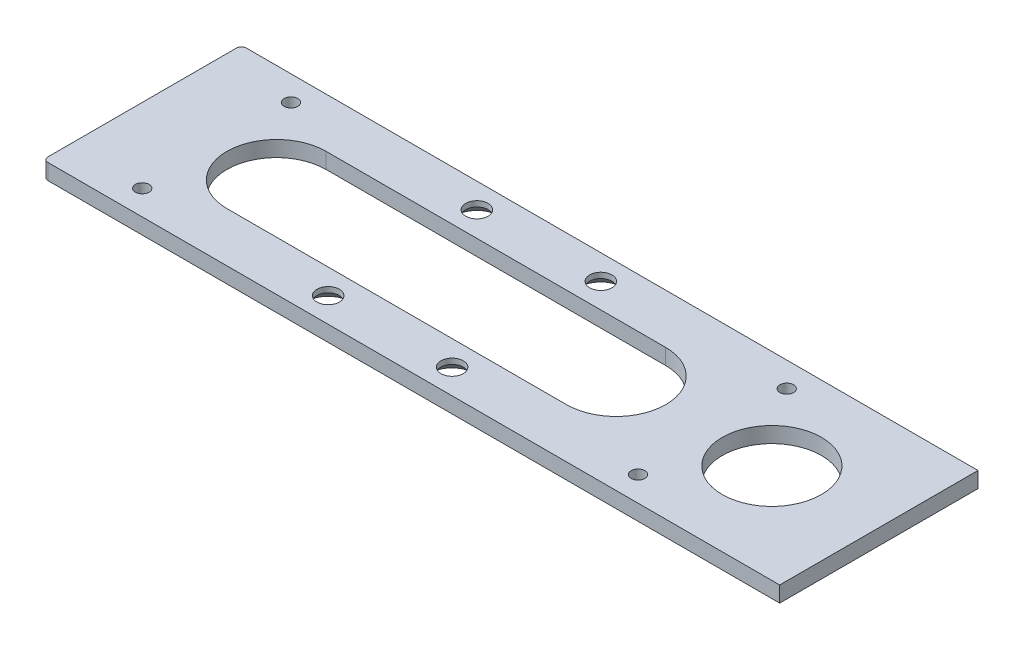
SolidWorks part; units mm, degrees
note: The reader was unsure of these and kept them because the rebuilt part matched: thickness of "Brida base1", "Chapa metálica1", "Chapa metálica2", "Chapa metálica5", "Sheet-Metal6".
ref_plane "Alzado" through (0, 0, 0) normal (0, 0, 1) x (1, 0, 0)
ref_plane "Planta" through (0, 0, 0) normal (0, 1, 0) x (1, 0, 0)
ref_plane "Vista lateral" through (0, 0, 0) normal (1, 0, 0) x (0, 0, -1)
sketch "Croquis1" plane through (0, 0, 0) normal (0, 1, 0) x (1, 0, 0)
  line L1 (-149.7778, 34.4444) -> (147.3722, 34.4444)
  line L2 (-149.7778, 34.4444) -> (-149.7778, -45.5556)
  line L3 (-149.7778, -45.5556) -> (147.3722, -45.5556)
  line L4 (147.3722, 34.4444) -> (147.3722, -45.5556)
  dimension "k" = 297.15
  dimension "D2" = 80
base flange "Brida base1" sketch "Croquis1" thickness 6.35 reverse thickness direction no parameters "D1"=10
fillet "Redondeo1" radius 2 2 edges at (-149.7778, -3.175, -34.4444) (-149.7778, -3.175, 45.5556)
hole_wizard "Taladro de margen para M51" positions "Croquis7" profile "Croquis6" hole size "M5" standard "Ansi Metric" end condition through all
sketch "Croquis7" plane through (0, 0, 0) normal (0, 1, 0) x (1, 0, 0)
  line L0 (-149.7778, 32.4444) -> (-149.7778, -43.5556) construction
  line L11 (-149.7778, -5.5556) -> (147.3722, -5.5556) construction
  line L12 (147.3722, -45.5556) -> (147.3722, 34.4444) construction
  point P0 (-119.7778, 24.4444)
  point P2 (-119.7778, -35.5556)
  point P4 (80.2222, -35.5556)
  point P45 (80.2222, 24.4444)
  dimension "D1" = 30
  dimension "D2" = 30
  dimension "D3" = 60
sketch "Croquis6" plane through (-119.7778, 0, -24.4444) normal (1, 0, 0) x (0, 0, 1)
  line L0 (0, 0) -> (0, 6.35)
  line L1 (0, 6.35) -> (2.75, 6.35)
  line L2 (2.75, 6.35) -> (2.75, 0)
  line L5 (2.75, 0) -> (0, 0)
  line L11 (0, -6.35) -> (0, 107.95) construction
  dimension "Diámetro de taladro hasta el siguiente" = 5.5
  dimension "Profundidad de taladro hasta el siguiente" = 6.35
sketch "Croquis8" plane through (0, 0, 0) normal (0, 1, 0) x (1, 0, 0)
  line L0 (-149.7778, -5.5556) -> (147.3722, -5.5556) construction
  line L1 (-149.7778, 32.4444) -> (-149.7778, -43.5556) construction
  line L2 (147.3722, -45.5556) -> (147.3722, 34.4444) construction
  line L3 (-0.2028, 34.4444) -> (-0.2028, -45.5556) construction
  line L5 (-147.7778, -45.5556) -> (147.3722, -45.5556) construction
  line L6 (147.3722, 34.4444) -> (-147.7778, 34.4444) construction
sketch "Croquis9" plane through (0, -6.35, 0) normal (0, -1, 0) x (-1, 0, 0)
  line L0 (-41.3891, -5.5556) -> (95.6281, -5.5556) construction
  line L1 (-41.3891, 14.4444) -> (95.6281, 14.4444)
  line L2 (-41.3891, -25.5556) -> (95.6281, -25.5556)
  line L3 (149.7778, -5.5556) -> (-147.3722, -5.5556) construction
  line L4 (149.7778, 32.4444) -> (149.7778, -43.5556) construction
  line L5 (-147.3722, -45.5556) -> (-147.3722, 34.4444) construction
  line L6 (-147.3722, 34.4444) -> (147.7778, 34.4444) construction
  arc A0 (-41.3891, 14.4444) -> (-41.3891, -25.5556) centre (-41.3891, -5.5556) ccw
  arc A1 (95.6281, -25.5556) -> (95.6281, 14.4444) centre (95.6281, -5.5556) ccw
  circle A2 centre (-104.2099, -5.5556) radius 20
  point P2 (27.1195, -5.5556)
  dimension "D2" = 40
  dimension "D1" = 20
extrude "Cortar-Extruir1" cut sketch "Croquis9" against normal blind 10 contours A2 | L1 A1 L2 A0 normal cut yes
sketch "Sketch1" plane through (0, -6.35, 0) normal (0, -1, 0) x (1, 0, 0)
  line L0 (-149.7778, 5.5556) -> (-64.7778, 5.5556) construction
  line L1 (-64.7778, 5.5556) -> (-64.7778, 45.5556) construction
  line L2 (-64.7778, 5.5556) -> (-64.7778, -34.4444) construction
  line L3 (-64.7778, 5.5556) -> (25.2222, 5.5556) construction
  line L4 (-149.7778, 43.5556) -> (-149.7778, -32.4444)
  line L5 (-147.7778, -34.4444) -> (147.3722, -34.4444)
  line L6 (147.3722, -34.4444) -> (147.3722, 45.5556)
  line L7 (147.3722, 45.5556) -> (-147.7778, 45.5556)
  line L8 (-149.7778, 43.5556) -> (-149.7778, -32.4444) construction
  line L9 (-147.7778, -34.4444) -> (147.3722, -34.4444) construction
  line L10 (147.3722, -34.4444) -> (147.3722, 45.5556) construction
  line L11 (147.3722, 45.5556) -> (-147.7778, 45.5556) construction
  line L12 (25.2222, 5.5556) -> (25.2222, 45.5556) construction
  line L13 (25.2222, 5.5556) -> (25.2222, -34.4444) construction
  line L14 (41.3891, 25.5556) -> (-95.6281, 25.5556) construction
  line L15 (41.3891, -14.4444) -> (-95.6281, -14.4444) construction
  line L16 (41.3891, 25.5556) -> (-95.6281, 25.5556) construction
  line L17 (41.3891, -14.4444) -> (-95.6281, -14.4444) construction
  line L18 (-64.7778, -34.4444) -> (-64.7778, -24.4444) construction
  line L19 (-64.7778, -24.4444) -> (-44.7778, -24.4444) construction
  line L20 (25.2222, -34.4444) -> (25.2222, -24.4444)
  line L21 (25.2222, -24.4444) -> (5.2222, -24.4444)
  circle A0 centre (-44.7778, -24.4444) radius 4.5
  circle A1 centre (5.2222, -24.4444) radius 4.5
  arc A2 (-149.7778, -32.4444) -> (-147.7778, -34.4444) centre (-147.7778, -32.4444) ccw
  arc A3 (-147.7778, 45.5556) -> (-149.7778, 43.5556) centre (-147.7778, 43.5556) ccw
  arc A4 (-149.7778, -32.4444) -> (-147.7778, -34.4444) centre (-147.7778, -32.4444) ccw construction
  arc A5 (-147.7778, 45.5556) -> (-149.7778, 43.5556) centre (-147.7778, 43.5556) ccw construction
  circle A6 centre (5.2222, 35.5556) radius 4.5
  circle A7 centre (-44.7778, 35.5556) radius 4.5
  dimension "D7" = 9
  dimension "D8" = 9
  dimension "D2" = 85
  dimension "D3" = 90
  dimension "D4" = 10
  dimension "D5" = 20
  dimension "D6" = 20
  dimension "D1" = 0
hole_wizard "CSK for M8 Oval Head Machine Screw1" positions "3DSketch1" profile "Sketch2" countersink size "M8" standard "ANSI Metric"
sketch3d "3DSketch1"
  point P0 (-44.7778, -6.35, -24.4444)
  point P3 (5.2222, -6.35, -24.4444)
  point P6 (5.2222, -6.35, 35.5556)
  point P9 (-44.7778, -6.35, 35.5556)
sketch "Sketch2" plane through (-44.7778, -6.35, -24.4444) normal (1, 0, 0) x (0, 0, -1)
  line L0 (0, 0) -> (0, 9.0529)
  line L1 (0, 9.0529) -> (4.5, 6.349)
  line L2 (4.5, 6.349) -> (4.5, 4.15)
  line L3 (4.5, 4.15) -> (8.65, 0)
  line L5 (8.65, 0) -> (0, 0)
  line L6 (-4.5, 4.15) -> (-8.65, 0) construction
  line L10 (0, 9.0529) -> (-4.5, 6.349) construction
  line L11 (0, -6.35) -> (0, 107.95) construction
  dimension "Hole Dia." = 9
  dimension "Hole Depth" = 6.349
  dimension "Near C'Sink Dia." = 17.3
  dimension "Near C'Sink Angle" = 90
  dimension "Drill Angle" = 118
sketch "Líneas de pliegue1" [suppressed] plane through (0, 0, 0) normal (0, 1, 0) x (1, 0, 0)
sketch "Cuadro delimitador1" [suppressed] plane through (0, 0, 0) normal (0, 1, 0) x (1, 0, 0)
sheet metal parameters "Chapa metálica1" thickness 6.35 parameters "D1"=10, "D7"=3
flat pattern "Chapa desplegada1" [suppressed]
sketch "Líneas de pliegue2" plane through (0, 0, 0) normal (0, 1, 0) x (1, 0, 0)
sketch3d "Cuadro delimitador2" [suppressed]
  line L0 (-149.7778, -85.5554, 0) -> (110.2222, -85.5556, 0) construction
  line L1 (-149.7777, 34.4444, 0) -> (110.2223, 34.4443, 0) construction
  line L2 (-149.7778, -85.5554, 0) -> (-149.7777, 34.4444, 0) construction
  line L3 (110.2222, -85.5556, 0) -> (110.2223, 34.4443, 0) construction
sheet metal parameters "Chapa metálica2" thickness 6.35 parameters "D1"=10
flat pattern "Chapa desplegada1"
sketch "Líneas de pliegue2" plane through (0, 0, 0) normal (0, 1, 0) x (1, 0, 0)
sketch3d "Cuadro delimitador2" [suppressed]
  line L0 (-149.7778, -45.5554, 0) -> (147.3722, -45.5556, 0) construction
  line L1 (-149.7777, 34.4444, 0) -> (147.3723, 34.4443, 0) construction
  line L2 (-149.7778, -45.5554, 0) -> (-149.7777, 34.4444, 0) construction
  line L3 (147.3722, -45.5556, 0) -> (147.3723, 34.4443, 0) construction
sheet metal parameters "Chapa metálica5" thickness 6.35 parameters "D1"=10
flat pattern "Chapa desplegada1"
sketch "Líneas de pliegue2" plane through (0, 0, 0) normal (0, 1, 0) x (1, 0, 0)
sketch3d "Cuadro delimitador2" [suppressed]
  line L0 (-149.7778, -45.5554, 0) -> (147.3722, -45.5556, 0) construction
  line L1 (-149.7777, 34.4444, 0) -> (147.3723, 34.4443, 0) construction
  line L2 (-149.7778, -45.5554, 0) -> (-149.7777, 34.4444, 0) construction
  line L3 (147.3722, -45.5556, 0) -> (147.3723, 34.4443, 0) construction
sheet metal parameters "Sheet-Metal6" thickness 6.35 parameters "D1"=10
flat pattern "Chapa desplegada1" [suppressed]
sketch "Líneas de pliegue2" plane through (0, 0, 0) normal (0, 1, 0) x (1, 0, 0)
sketch3d "Cuadro delimitador2" [suppressed]
  line L0 (-149.7778, -45.5554, 0) -> (147.3722, -45.5556, 0) construction
  line L1 (-149.7777, 34.4444, 0) -> (147.3723, 34.4443, 0) construction
  line L2 (-149.7778, -45.5554, 0) -> (-149.7777, 34.4444, 0) construction
  line L3 (147.3722, -45.5556, 0) -> (147.3723, 34.4443, 0) construction
sketch "Sketch1-1" [suppressed] plane through (0, -6.35, 0) normal (0, -1, 0) x (1, 0, 0)
  line L0 (-149.7778, 5.5556) -> (-64.7778, 5.5556) construction
  line L1 (-64.7778, 5.5556) -> (-64.7778, 45.5556) construction
  line L2 (-64.7778, 5.5556) -> (-64.7778, -34.4444) construction
  line L3 (-64.7778, 5.5556) -> (25.2222, 5.5556) construction
  line L8 (-149.7778, 43.5556) -> (-149.7778, -32.4444) construction
  line L9 (-147.7778, -34.4444) -> (147.3722, -34.4444) construction
  line L10 (147.3722, -34.4444) -> (147.3722, 45.5556) construction
  line L11 (147.3722, 45.5556) -> (-147.7778, 45.5556) construction
  line L12 (25.2222, 5.5556) -> (25.2222, 45.5556) construction
  line L13 (25.2222, 5.5556) -> (25.2222, -34.4444) construction
  line L16 (41.3891, 25.5556) -> (-95.6281, 25.5556) construction
  line L17 (41.3891, -14.4444) -> (-95.6281, -14.4444) construction
  line L18 (-64.7778, -34.4444) -> (-64.7778, -24.4444) construction
  line L19 (-64.7778, -24.4444) -> (-44.7778, -24.4444) construction
  line L20 (25.2222, -34.4444) -> (25.2222, -24.4444)
  line L21 (25.2222, -24.4444) -> (5.2222, -24.4444)
  circle A0 centre (-44.7778, -24.4444) radius 4.5
  circle A1 centre (5.2222, -24.4444) radius 4.5
  arc A4 (-149.7778, -32.4444) -> (-147.7778, -34.4444) centre (-147.7778, -32.4444) ccw construction
  arc A5 (-147.7778, 45.5556) -> (-149.7778, 43.5556) centre (-147.7778, 43.5556) ccw construction
  circle A6 centre (5.2222, 35.5556) radius 4.5
  circle A7 centre (-44.7778, 35.5556) radius 4.5
  dimension "D7" = 9
  dimension "D8" = 9
  dimension "D2" = 85
  dimension "D3" = 90
  dimension "D4" = 10
  dimension "D5" = 20
  dimension "D6" = 20
